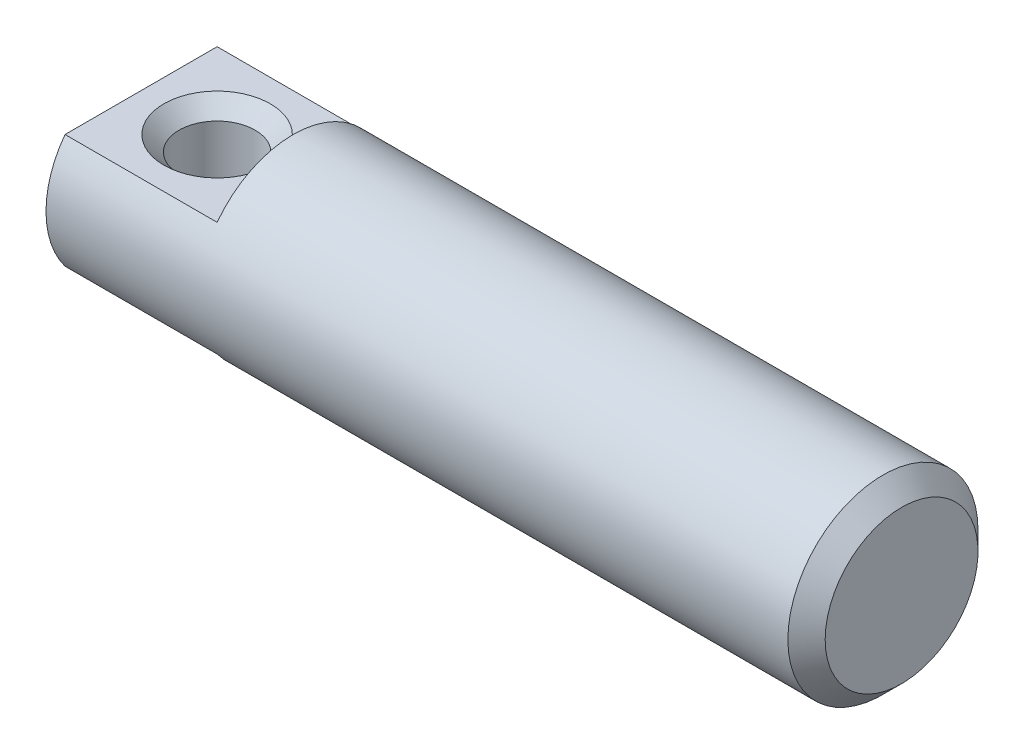
SolidWorks part; units mm, degrees
ref_plane "Front Plane" through (0, 0, 0) normal (0, 0, 1) x (1, 0, 0)
ref_plane "Top Plane" through (0, 0, 0) normal (0, 1, 0) x (1, 0, 0)
ref_plane "Right Plane" through (0, 0, 0) normal (1, 0, 0) x (0, 0, -1)
ref_plane "Plane1" through (0, 0, 0) normal (0, 0, 1) x (1, 0, 0)
sketch "Sketch1" plane through (0, 0, 0) normal (0, 0, 1) x (1, 0, 0)
  line L0 (0, 0) -> (0, 2.5)
  line L1 (0, 2.5) -> (19.5095, 2.5)
  line L2 (19.5095, 2.5) -> (20, 2.0095)
  line L3 (20, 2.0095) -> (20, 0)
  line L4 (20, 0) -> (0, 0)
  line L5 (20, 0) -> (0, 0) construction
revolve "Revolve1" add sketch "Sketch1" angle 360 about L5 reverse direction yes
ref_plane "Plane2" through (0, 0, 0) normal (0, 0, 1) x (1, 0, 0)
sketch "Sketch2" plane through (0, 0, 0) normal (0, 0, 1) x (1, 0, 0)
  line L0 (-1, 3) -> (-1, -3)
  line L1 (-1, -3) -> (4, -3)
  line L2 (4, -3) -> (4, -1.5)
  line L3 (4, -1.5) -> (0, -1.5)
  line L4 (0, -1.5) -> (0, 1.5)
  line L5 (0, 1.5) -> (4, 1.5)
  line L6 (4, 1.5) -> (4, 3)
  line L7 (4, 3) -> (-1, 3)
extrude "Cut-Extrude1" cut sketch "Sketch2" against normal blind 2.5 and the other way blind 2.5
ref_plane "Plane3" through (0, 0, 0) normal (0, 0, 1) x (1, 0, 0)
sketch "Sketch3" plane through (0, 0, 0) normal (0, 0, 1) x (1, 0, 0)
  line L0 (2, 1.5) -> (3.4, 1.5)
  line L1 (3.4, 1.5) -> (3, 1.1)
  line L2 (3, 1.1) -> (3, -1.1)
  line L3 (3, -1.1) -> (3.4, -1.5)
  line L4 (3.4, -1.5) -> (2, -1.5)
  line L5 (2, -1.5) -> (2, 1.5)
  line L6 (2, -1.5) -> (2, 1.5) construction
revolve "Cut-Revolve1" cut sketch "Sketch3" angle 360 about L6 reverse direction yes
